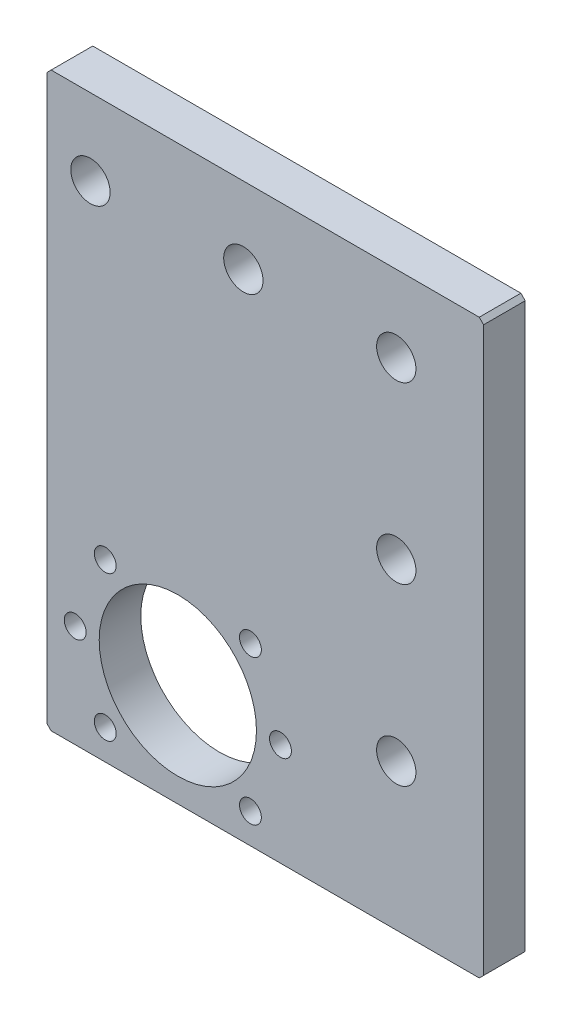
SolidWorks part; units mm, degrees
material "6061-T6 (SS)"
ref_plane "Front Plane" through (0, 0, 0) normal (0, 0, 1) x (1, 0, 0)
ref_plane "Top Plane" through (0, 0, 0) normal (0, 1, 0) x (1, 0, 0)
ref_plane "Right Plane" through (0, 0, 0) normal (1, 0, 0) x (0, 0, -1)
sketch "Sketch1" plane through (0, 0, 0) normal (0, 0, 1) x (1, 0, 0)
  line L0 (-20, 90) -> (15, 90) construction
  line L1 (-30, -23.5) -> (70, -23.5)
  line L2 (-30, -23.5) -> (-30, 107.5)
  line L3 (-30, 107.5) -> (70, 107.5)
  line L4 (70, -23.5) -> (70, 107.5)
  line L5 (15, 90) -> (50, 90) construction
  line L6 (50, 90) -> (50, 50) construction
  line L7 (50, 50) -> (50, 10) construction
  line L8 (0, -55) -> (0, 55) construction
  line L9 (0, 23.5) -> (-16.617, 16.617) construction
  line L10 (-16.617, 16.617) -> (-23.5, 0) construction
  line L11 (-23.5, 0) -> (-16.617, -16.617) construction
  line L12 (-16.617, -16.617) -> (0, -23.5) construction
  line L13 (0, -23.5) -> (16.617, -16.617) construction
  line L14 (16.617, -16.617) -> (23.5, 0) construction
  line L15 (23.5, 0) -> (16.617, 16.617) construction
  line L16 (16.617, 16.617) -> (0, 23.5) construction
  circle A0 centre (0, 0) radius 18
  circle A1 centre (0, 0) radius 21.7112 construction
  point P12 (0, 0)
  dimension "D1" = 36
  dimension "D2" = 100
  dimension "D3" = 23.5
  dimension "D4" = 17.5
  dimension "D5" = 70
  dimension "D6" = 40
  dimension "D7" = 10
  dimension "D8" = 20
  dimension "D9" = 10
  dimension "D10" = 47
extrude "Boss-Extrude1" add sketch "Sketch1" along normal mid plane 9.525
hole_wizard "M8 Clearance Hole1" positions "Sketch2" profile "Sketch3" hole size "M8" standard "ANSI Metric" end condition up to next
sketch "Sketch2" plane through (0, 0, 4.7625) normal (0, 0, 1) x (1, 0, 0)
  point P0 (-20, 90)
  point P3 (15, 90)
  point P6 (50, 90)
  point P9 (50, 50)
  point P12 (50, 10)
sketch "Sketch3" plane through (-20, 90, 4.7625) normal (1, 0, 0) x (0, -1, 0)
  line L0 (0, 0) -> (0, 9.525)
  line L1 (0, 9.525) -> (4.5, 9.525)
  line L2 (4.5, 9.525) -> (4.5, 0)
  line L5 (4.5, 0) -> (0, 0)
  line L11 (0, -6.35) -> (0, 107.95) construction
  dimension "Thru Hole Dia." = 9
  dimension "Thru Hole Depth" = 9.525
hole_wizard "M6x1.0 Tapped Hole1" positions "Sketch4" profile "Sketch5" tap size "M6x1.0" standard "ANSI Metric" end condition up to next
sketch "Sketch4" plane through (0, 0, 4.7625) normal (0, 0, 1) x (1, 0, 0)
  point P3 (16.617, 16.617)
  point P6 (23.5, 0)
  point P9 (16.617, -16.617)
  point P12 (-16.617, -16.617)
  point P15 (-23.5, 0)
  point P18 (-16.617, 16.617)
  point P22 (0, 0)
sketch "Sketch5" plane through (16.617, 16.617, 4.7625) normal (1, 0, 0) x (0, -1, 0)
  line L0 (0, 0) -> (0, 9.525)
  line L1 (0, 9.525) -> (2.5, 9.525)
  line L2 (2.5, 9.525) -> (2.5, 0)
  line L5 (2.5, 0) -> (0, 0)
  line L11 (0, -6.35) -> (0, 107.95) construction
  dimension "Thru Tap Drill Dia." = 5
  dimension "Thru Tap Drill Depth" = 9.525
cosmetic thread "Hole Thread1"
cosmetic thread "Hole Thread2"
cosmetic thread "Hole Thread3"
cosmetic thread "Hole Thread4"
cosmetic thread "Hole Thread5"
cosmetic thread "Hole Thread6"
chamfer "Chamfer1" distance 1 angle 45 4 edges at (-30, -23.5, 0) (70, -23.5, 0) (70, 107.5, 0) (-30, 107.5, 0)
